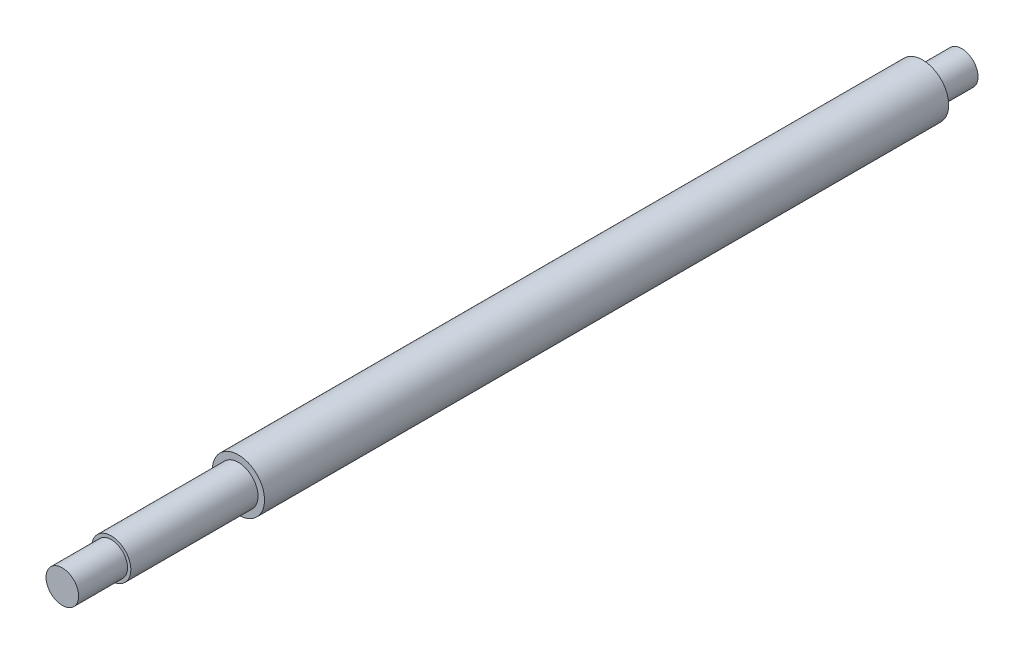
SolidWorks part; units mm, degrees
ref_plane "Front Plane" through (0, 0, 0) normal (0, 0, 1) x (1, 0, 0)
ref_plane "Top Plane" through (0, 0, 0) normal (0, 1, 0) x (1, 0, 0)
ref_plane "Right Plane" through (0, 0, 0) normal (1, 0, 0) x (0, 0, -1)
sketch "Sketch1" plane through (0, 0, 0) normal (1, 0, 0) x (0, 0, -1)
  line L0 (0, 0) -> (-42.623, 0) construction
  line L1 (-275.75, 0) -> (-275.75, 5)
  line L2 (-275.75, 5) -> (-260.75, 5)
  line L3 (-260.75, 5) -> (-260.75, 6)
  line L4 (-260.75, 6) -> (-221.75, 6)
  line L5 (-221.75, 6) -> (-221.75, 8)
  line L6 (-221.75, 8) -> (-12, 8)
  line L7 (-12, 8) -> (-12, 5)
  line L8 (-12, 5) -> (0, 5)
  line L9 (0, 5) -> (0, 0)
  line L10 (-275.75, 0) -> (0, 0)
  dimension "D1" = 5
  dimension "D2" = 6
  dimension "D3" = 8
  dimension "D4" = 5
  dimension "D5" = 12
  dimension "D6" = 39
  dimension "D7" = 15
  dimension "D8" = 209.75
revolve "Revolve1" add sketch "Sketch1" angle 360 about L0
